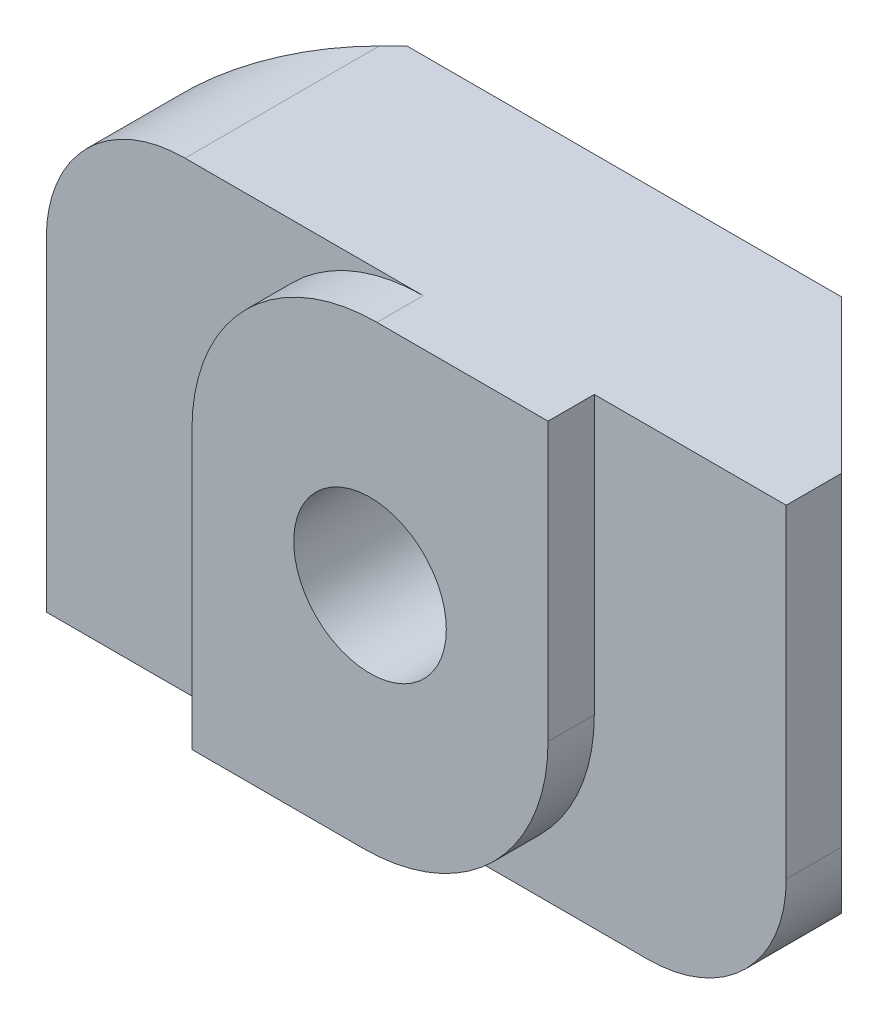
SolidWorks part; units mm, degrees
ref_plane "Front Plane" through (0, 0, 0) normal (0, 0, 1) x (1, 0, 0)
ref_plane "Top Plane" through (0, 0, 0) normal (0, 1, 0) x (1, 0, 0)
ref_plane "Right Plane" through (0, 0, 0) normal (1, 0, 0) x (0, 0, -1)
sketch "Sketch1" plane through (0, 0, 0) normal (0, 1, 0) x (1, 0, 0)
  line L0 (4.7, 0) -> (-4.7, 0)
  line L1 (-4.7, 0) -> (-8, -3.3)
  line L2 (-8, -3.3) -> (-8, -4.5)
  line L3 (-8, -4.5) -> (-3.85, -4.5)
  line L4 (-3.85, -4.5) -> (-3.85, -5.5)
  line L5 (-3.85, -5.5) -> (3.85, -5.5)
  line L6 (0, -5.5) -> (0, 0) construction
  line L7 (3.85, -4.5) -> (3.85, -5.5)
  line L8 (8, -4.5) -> (3.85, -4.5)
  line L9 (8, -3.3) -> (8, -4.5)
  line L10 (4.7, 0) -> (8, -3.3)
  line L11 (-3.85, -4.5) -> (3.85, -4.5) construction
  dimension "D1" = 3.85
  dimension "D2" = 1
  dimension "D3" = 45
  dimension "D4" = 8
  dimension "D5" = 4.5
  dimension "D6" = 1.2
extrude "Boss-Extrude1" add sketch "Sketch1" along normal blind 10
sketch "Sketch2" plane through (0, 0, 5.5) normal (0, 0, 1) x (1, 0, 0)
  line L0 (0, 0) -> (0, 10) construction
  line L1 (-3.85, 10) -> (3.85, 10) construction
  circle A0 centre (0, 5) radius 1.65
  dimension "D1" = 3.3
extrude "Cut-Extrude1" cut sketch "Sketch2" against normal through all
fillet "Fillet1" radius 4 2 edges at (-3.85, 10, 5) (3.85, 0, 5)
fillet "Fillet2" radius 3 2 edges at (-8, 10, 3.9) (8, 0, 3.9)
